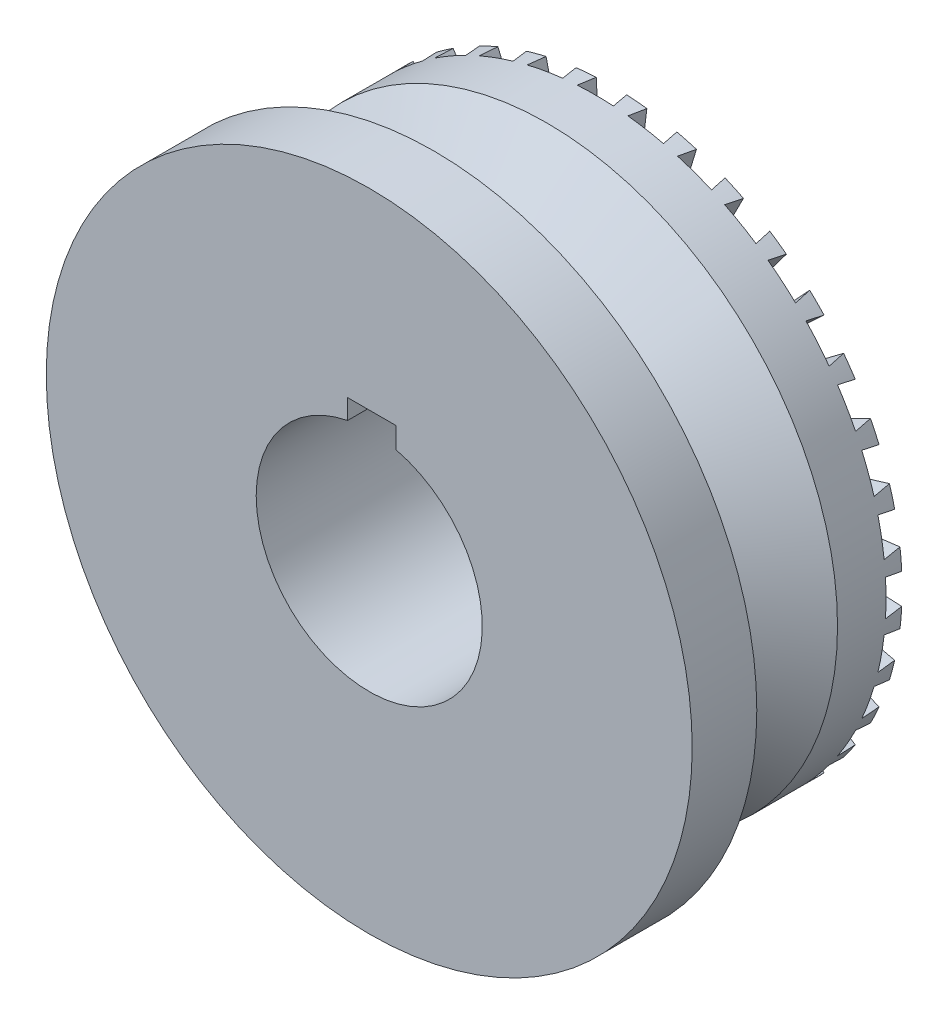
SolidWorks part; units mm, degrees
ref_plane "前视基准面" through (0, 0, 0) normal (0, 0, 1) x (1, 0, 0)
ref_plane "上视基准面" through (0, 0, 0) normal (0, 1, 0) x (1, 0, 0)
ref_plane "右视基准面" through (0, 0, 0) normal (1, 0, 0) x (0, 0, -1)
other "Configuration Table"
sketch "草图1" plane through (0, 0, 0) normal (1, 0, 0) x (0, 0, -1)
  line L0 (0, 28.0393) -> (0, -27.7468) construction
  line L1 (-7, 20) -> (-7, 0)
  line L2 (-7, 20) -> (-3, 20)
  line L3 (-3, 20) -> (-3, 13)
  line L4 (-3, 13) -> (0, 13)
  line L5 (0, 13) -> (4, 18)
  line L6 (4, 18) -> (8, 18)
  line L7 (8, 18) -> (8, 0)
  line L8 (-22.3796, 0) -> (30.6362, 0) construction
  line L9 (-7, 0) -> (8, 0)
  dimension "D1" = 40
  dimension "D2" = 15
  dimension "D3" = 4
  dimension "D4" = 3
  dimension "D5" = 4
  dimension "D6" = 5
  dimension "D7" = 36
  dimension "D8" = 7
revolve "旋转1" add sketch "草图1" angle 360 about L9
sketch "草图2" plane through (0, 0, -8) normal (0, 0, -1) x (-1, 0, 0)
  circle A0 centre (0, 0) radius 7
  circle A1 centre (0, 0) radius 10
  dimension "D1" = 20
  dimension "D2" = 14
extrude "切除-拉伸1" cut sketch "草图2" against normal blind 4 contours A0 | A1
extrude "切除-拉伸2" cut sketch "草图2<3>" against normal up to next contours A0 region at (0, 0, -8)
sketch "草图2<3>" plane through (0, 0, -8) normal (0, 0, -1) x (-1, 0, 0) same geometry as "草图2"
sketch "草图3" plane through (0, 0, -8) normal (0, 0, -1) x (-1, 0, 0)
  line L0 (0, 40.6213) -> (0, -25.7618) construction
  line L1 (-0.942, 17.9753) -> (0, 0)
  line L2 (0, 0) -> (0.942, 17.9753)
  circle A0 centre (0, 0) radius 18 construction
  arc A1 (0.942, 17.9753) -> (-0.942, 17.9753) centre (0, 0) ccw
  point P7 (0, 0)
  dimension "D1" = 6
extrude "切除-拉伸6" cut sketch "草图3" against normal blind 1 draft 10 draft outward yes
pattern_circular "阵列(圆周)1" count 36 over 360 about axis through (0, 0, -4) along (0, 0, 1) of "切除-拉伸6"
sketch "草图4" plane through (0, 0, -4) normal (0, 0, -1) x (-1, 0, 0)
  line L0 (-0.1593, 19.2462) -> (-0.1593, -10.0081) construction
  line L1 (-1.6593, 6.8005) -> (-1.6593, 8.1)
  line L2 (-1.6593, 8.1) -> (1.3407, 8.1)
  line L3 (1.3407, 6.8005) -> (1.3407, 8.1)
  circle A0 centre (0, 0) radius 7 construction
  arc A1 (1.3407, 6.8704) -> (-1.6593, 6.8005) centre (0, 0) ccw
  point P4 (-0.1593, 8.1)
  circle M4 centre (0, 0) radius 7
  dimension "D1" = 3
  dimension "D2" = 8.1
  dimension "D3" = 1.2995
extrude "切除-拉伸7" cut sketch "草图4" against normal through all contours L0 L2 L1 M4 | L2 L0 A1 L3 region at (-0.6047, 7.5301, -4) region at (0.9303, 7.512, -4)
